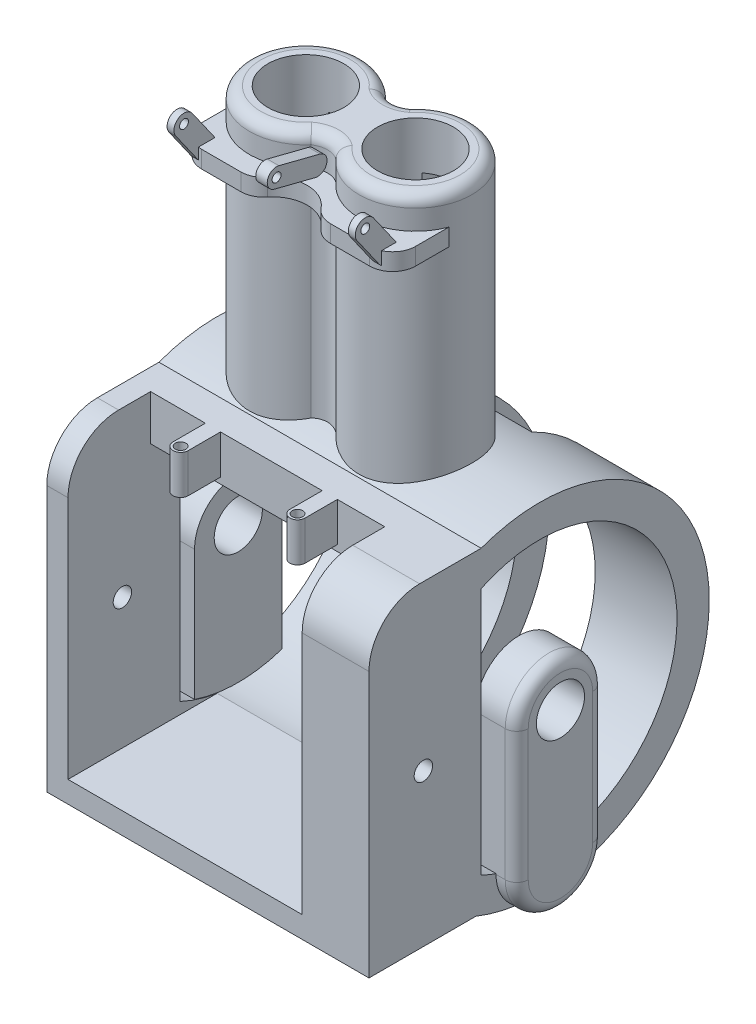
SolidWorks part; units mm, degrees
ref_plane "Ön Düzlem" through (0, 0, 0) normal (0, 0, 1) x (1, 0, 0)
ref_plane "Üst Düzlem" through (0, 0, 0) normal (0, 1, 0) x (1, 0, 0)
ref_plane "Sağ Düzlem" through (0, 0, 0) normal (1, 0, 0) x (0, 0, -1)
sketch "Çizim2" plane through (0, 0, 0) normal (0, 1, 0) x (1, 0, 0)
  line L0 (-55, 0) -> (55, 0) construction
  circle A0 centre (0, 0) radius 16.5
  circle A1 centre (-47.6265, 0) radius 16.5
  arc A2 (-29.2049, 16.1522) -> (-29.2049, -16.1522) centre (-47.6265, 0) ccw
  arc A3 (-18.4217, -16.1522) -> (-18.4217, 16.1522) centre (0, 0) ccw
  arc A4 (-29.2049, -16.1522) -> (-18.4217, -16.1522) centre (-23.8133, -23.9147) cw
  arc A5 (-29.2049, 16.1522) -> (-18.4217, 16.1522) centre (-23.8133, 23.9147) ccw
  circle A6 centre (-47.6265, 0) radius 24.5 construction
  circle A7 centre (0, 0) radius 24.5 construction
  point P5 (0, 0)
  point P10 (0, 0)
  point P19 (-29.2049, 16.1522)
  point P21 (0, 0)
  point P22 (-48.2806, 0)
  dimension "D1" = 33
  dimension "D2" = 8
  dimension "D3" = 8
extrude "Yükseklik-Ekstrüzyon1" add sketch "Çizim2" along normal blind 120 contours A5 A2 A4 A3 A1 A0 region at (-23.8133, 0, 0)
ref_plane "Düzlem1" through (0, 0, -32.0546) normal (0, 0, 1) x (1, 0, 0)
sketch "Çizim3" plane through (0, 0, -32.0546) normal (0, 0, 1) x (1, 0, 0)
  line L1 (10.3867, 99.4019) -> (-10.1113, 99.4019)
  line L2 (10.3867, 99.4019) -> (10.3867, 32.5179)
  line L3 (10.3867, 32.5179) -> (-10.1113, 32.5179)
  line L4 (-10.1113, 99.4019) -> (-10.1113, 32.5179)
  line L5 (-33.6449, 99.4019) -> (-53.2176, 99.4019)
  line L6 (-33.6449, 99.4019) -> (-33.6449, 32.5179)
  line L7 (-33.6449, 32.5179) -> (-53.2176, 32.5179)
  line L8 (-53.2176, 99.4019) -> (-53.2176, 32.5179)
extrude "Kes-Ekstrüzyon1" cut sketch "Çizim3" along normal blind 26
sketch "Çizim6" plane through (0, 0, 0) normal (1, 0, 0) x (0, 0, -1)
  circle A0 centre (0, -59.6459) radius 59.6459
  circle A1 centre (0, -59.6459) radius 73.6459
  point P5 (0, 0)
  point P6 (0, 0)
  dimension "D1" = 14
extrude "Yükseklik-Ekstrüzyon2" add sketch "Çizim6" along normal blind 54 and the other way blind 86
sketch "Çizim7" plane through (0, 120, 0) normal (0, 1, 0) x (1, 0, 0)
  circle A0 centre (-47.6265, 0) radius 16.5
  circle A1 centre (0, 0) radius 16.5
extrude "Kes-Ekstrüzyon3" cut sketch "Çizim7" against normal blind 228
sketch "Çizim8" plane through (0, 120, 0) normal (0, 1, 0) x (1, 0, 0)
  line L0 (-77, 32.0546) -> (77, 32.0546) construction
  line L1 (-66.2257, 93.0344) -> (-33.3817, 93.0344)
  line L2 (-66.2257, 93.0344) -> (-66.2257, 32.0546)
  line L3 (-66.2257, 32.0546) -> (-33.3817, 32.0546)
  line L4 (-33.3817, 93.0344) -> (-33.3817, 32.0546)
  line L5 (-15.5317, 93.2129) -> (18.4546, 93.2129)
  line L6 (-15.5317, 93.2129) -> (-15.5317, 32.0546)
  line L7 (-15.5317, 32.0546) -> (18.4546, 32.0546)
  line L8 (18.4546, 93.2129) -> (18.4546, 32.0546)
  line L10 (-54.9588, -91.8557) -> (17.8794, -91.8557)
  line L11 (-54.9588, -91.8557) -> (-54.9588, -45.5266)
  line L12 (-54.9588, -45.5266) -> (17.8794, -45.5266)
  line L13 (17.8794, -91.8557) -> (17.8794, -45.5266)
extrude "Kes-Ekstrüzyon4" cut sketch "Çizim8" against normal blind 290
sketch "Çizim9" plane through (0, 0, 0) normal (1, 0, 0) x (0, 0, -1)
  line L1 (-32.9089, 106.3109) -> (0.9157, 106.3109)
  line L2 (-32.9089, 106.3109) -> (-32.9089, 98.8674)
  line L3 (-32.9089, 98.8674) -> (0.9157, 98.8674)
  line L4 (0.9157, 106.3109) -> (0.9157, 98.8674)
extrude "Yükseklik-Ekstrüzyon3" add sketch "Çizim9" along normal blind 23 and the other way blind 70
fillet "Radyus1" radius 10 2 edges at (23, 102.5892, 32.9089) (-70, 102.5892, 32.9089)
sketch "Çizim10" plane through (0, 120, 0) normal (0, 1, 0) x (1, 0, 0)
  circle A0 centre (0, 0) radius 16.5 construction
  circle A1 centre (-47.6265, 0) radius 16.5 construction
  circle A2 centre (0, 0) radius 16.5
  circle A3 centre (-47.6265, 0) radius 16.5
extrude "Kes-Ekstrüzyon5" cut sketch "Çizim10" against normal blind 37
sketch "Çizim11" plane through (0, 106.3109, 0) normal (0, 1, 0) x (1, 0, 0)
  line L0 (-60, -32.9089) -> (13, -32.9089) construction
  line L1 (-37.3649, -32.9089) -> (-9.6617, -32.9089)
  arc A0 (-37.3649, -32.9089) -> (-9.6617, -32.9089) centre (-23.5133, -38.4571) cw
extrude "Kes-Ekstrüzyon6" cut sketch "Çizim11" against normal blind 37
fillet "Radyus2" radius 10 2 edges at (-9.6617, 102.5892, 32.9089) (-37.3649, 102.5892, 32.9089)
ref_plane "Düzlem2" through (17.2344, 0, 0) normal (1, 0, 0) x (0, 0, -1)
ref_plane "Düzlem3" through (-64.5268, 0, 0) normal (1, 0, 0) x (0, 0, -1)
sketch "Çizim14" plane through (-64.5268, 0, 0) normal (1, 0, 0) x (0, 0, -1)
  line L0 (-39.0408, 117.8786) -> (-29.5117, 104.3179) construction
  line L1 (-35.4786, 120.3818) -> (-25.9494, 106.8211)
  line L2 (-42.6031, 115.3754) -> (-33.0739, 101.8147)
  arc A0 (-35.4786, 120.3818) -> (-42.6031, 115.3754) centre (-39.0408, 117.8786) ccw
  arc A1 (-33.0739, 101.8147) -> (-25.9494, 106.8211) centre (-29.5117, 104.3179) ccw
  point P2 (-34.2762, 111.0983)
extrude "Yükseklik-Ekstrüzyon4" add sketch "Çizim14" along normal blind 3
sketch "Çizim15" plane through (17.2344, 0, 0) normal (1, 0, 0) x (0, 0, -1)
  line L0 (-42.6031, 115.3754) -> (-33.0739, 101.8147) construction
  line L1 (-25.9494, 106.8211) -> (-35.4786, 120.3818) construction
  line L2 (-42.6031, 115.3754) -> (-33.0739, 101.8147)
  line L3 (-25.9494, 106.8211) -> (-35.4786, 120.3818)
  line L6 (-25.9494, 106.8211) -> (-35.4786, 120.3818)
  line L7 (-42.6031, 115.3754) -> (-33.0739, 101.8147)
  line L8 (-25.9494, 106.8211) -> (-35.4786, 120.3818)
  line L9 (-42.6031, 115.3754) -> (-33.0739, 101.8147)
  arc A0 (-33.0739, 101.8147) -> (-31.8256, 100.6299) centre (-29.5117, 104.3179) ccw construction
  arc A1 (-35.4786, 120.3818) -> (-42.6031, 115.3754) centre (-39.0408, 117.8786) ccw construction
  arc A2 (-33.0739, 101.8147) -> (-31.8256, 100.6299) centre (-29.5117, 104.3179) ccw
  arc A3 (-35.4786, 120.3818) -> (-42.6031, 115.3754) centre (-39.0408, 117.8786) ccw
  arc A6 (-33.0739, 101.8147) -> (-25.9494, 106.8211) centre (-29.5117, 104.3179) ccw
  arc A7 (-35.4786, 120.3818) -> (-42.6031, 115.3754) centre (-39.0408, 117.8786) ccw
  arc A8 (-33.0739, 101.8147) -> (-25.9494, 106.8211) centre (-29.5117, 104.3179) ccw
  arc A9 (-35.4786, 120.3818) -> (-42.6031, 115.3754) centre (-39.0408, 117.8786) ccw
  dimension "D1" = 0
extrude "Yükseklik-Ekstrüzyon5" add sketch "Çizim15" against normal blind 3 contours A2 A8 L3 A3 L2 region at (17.2344, 111.0983, 34.2762)
sketch "Çizim16" plane through (17.2344, 0, 0) normal (1, 0, 0) x (0, 0, -1)
  circle A0 centre (-39.0492, 118.1335) radius 1.9404
extrude "Kes-Ekstrüzyon7" cut sketch "Çizim16" against normal blind 129
ref_plane "Düzlem4" through (-23.8, 0, 0) normal (1, 0, 0) x (0, 0, -1)
sketch "Çizim17" plane through (-23.8, 0, 0) normal (1, 0, 0) x (0, 0, -1)
  line L0 (-39.0492, 118.1335) -> (-21.1782, 113.5807) construction
  line L1 (-38.0478, 122.0642) -> (-20.1768, 117.5114)
  line L2 (-40.0506, 114.2028) -> (-22.1795, 109.65)
  arc A0 (-38.0478, 122.0642) -> (-40.0506, 114.2028) centre (-39.0492, 118.1335) ccw
  arc A1 (-22.1795, 109.65) -> (-20.1768, 117.5114) centre (-21.1782, 113.5807) ccw
  circle A2 centre (-39.0492, 118.1335) radius 1.9404 construction
  circle A3 centre (-39.0492, 118.1335) radius 1.9404
  point P3 (-30.1137, 115.8571)
extrude "Yükseklik-Ekstrüzyon6" add sketch "Çizim17" along normal mid plane 5 separate body
sketch "Çizim18" plane through (54, 0, 0) normal (1, 0, 0) x (0, 0, -1)
  line L0 (0, -116.5192) -> (0, -59.6459) construction
  line L1 (-18.9961, -116.5192) -> (-18.9961, -59.6459)
  line L2 (18.9961, -116.5192) -> (18.9961, -59.6459)
  arc A0 (-18.9961, -116.5192) -> (18.9961, -116.5192) centre (0, -116.5192) ccw
  arc A1 (18.9961, -59.6459) -> (-18.9961, -59.6459) centre (0, -59.6459) ccw
  circle A2 centre (0, -59.6459) radius 10.4598
  point P3 (0, -88.0825)
extrude "Yükseklik-Ekstrüzyon7" add sketch "Çizim18" along normal mid plane 18
sketch "Çizim19" plane through (-86, 0, 0) normal (-1, 0, 0) x (0, 0, 1)
  line L0 (-18.9961, -116.5192) -> (-18.9961, -59.6459) construction
  line L1 (-18.9961, -116.5192) -> (-18.9961, -59.6459)
  line L2 (18.9961, -116.5192) -> (18.9961, -59.6459) construction
  line L3 (18.9961, -116.5192) -> (18.9961, -59.6459)
  circle A0 centre (0, -59.6459) radius 10.4598 construction
  arc A1 (18.9961, -59.6459) -> (-18.9961, -59.6459) centre (0, -59.6459) ccw construction
  circle A2 centre (0, -59.6459) radius 10.4598
  arc A3 (18.9961, -59.6459) -> (-18.9961, -59.6459) centre (0, -59.6459) ccw
  arc A4 (-18.9961, -116.5192) -> (18.9961, -116.5192) centre (0, -116.5192) ccw construction
  circle A5 centre (0, -59.6459) radius 73.6459 construction
  arc A6 (-18.9961, -116.5192) -> (18.9961, -116.5192) centre (0, -116.5192) ccw
  circle A7 centre (0, -59.6459) radius 73.6459
  circle M1 centre (0, -59.6459) radius 59.6459
  circle M2 centre (0, -59.6459) radius 73.6459
extrude "Yükseklik-Ekstrüzyon8" add sketch "Çizim19" along normal mid plane 18 contours L3 A3 L1 A2 M1 | L1 A6 L3 M2 M1 region at (-86, -124.9458, 0) region at (-86, -84.4294, 0)
fillet "Radyus3" radius 5 4 edges at (-23.8133, 120, 14.4634) (-23.8133, 120, -14.4634) (24.5, 120, 0) (-72.1265, 120, 0)
fillet "Radyus5" radius 5 4 edges at (63, -135.5153, 0) (63, -88.0825, 18.9961) (63, -40.6498, 0) (63, -88.0825, -18.9961)
fillet "Radyus6" radius 2 5 edges at (-95, -125.6989, 16.6308) (-95, -88.0825, 18.9961) (-95, -125.6989, -16.6308) (-95, -88.0825, -18.9961) (-95, -40.6498, 0)
sketch "Çizim20" plane through (54, 0, 0) normal (1, 0, 0) x (0, 0, -1)
  line L0 (-25.464, 9.4577) -> (-74.2014, 9.4577)
  line L1 (-25.464, 9.4577) -> (-25.464, -127.8857)
  line L2 (-74.2014, 9.4577) -> (-74.2014, -127.8857)
  line L3 (-25.464, -127.8857) -> (-74.2014, -127.8857)
  circle A0 centre (0, -59.6459) radius 73.6459 construction
extrude "Yükseklik-Ekstrüzyon9" add sketch "Çizim20" against normal blind 140
sketch "Çizim21" plane through (0, 9.4577, 0) normal (0, 1, 0) x (1, 0, 0)
  line L0 (-76.7794, -74.2014) -> (24.9661, -74.2014)
  line L1 (-76.7794, -74.2014) -> (-76.7794, -38.3195)
  line L2 (24.9661, -74.2014) -> (24.9661, -38.3195)
  line L3 (-76.7794, -38.3195) -> (24.9661, -38.3195)
  line L4 (-86, -74.2014) -> (54, -74.2014) construction
extrude "Kes-Ekstrüzyon8" cut sketch "Çizim21" against normal blind 128
sketch "Çizim22" plane through (0, 0, 38.3195) normal (0, 0, 1) x (1, 0, 0)
  line L0 (-76.7794, -118.5423) -> (24.9661, -118.5423)
  line L1 (-76.7794, -118.5423) -> (-76.7794, -10.1855)
  line L2 (24.9661, -118.5423) -> (24.9661, -10.1855)
  line L3 (-76.7794, -10.1855) -> (24.9661, -10.1855)
extrude "Kes-Ekstrüzyon9" cut sketch "Çizim22" against normal blind 42
sketch "Çizim23" plane through (54, 0, 0) normal (1, 0, 0) x (0, 0, -1)
  line L0 (-39.0492, 118.1335) -> (-39.0492, 77.2105) construction
  circle A0 centre (-50.5644, -61.758) radius 4
  point P3 (-50.5644, -61.758)
extrude "Kes-Ekstrüzyon10" cut sketch "Çizim23" against normal blind 161
fillet "Radyus7" radius 22 2 edges at (39.483, 9.4577, 74.2014) (-81.3897, 9.4577, 74.2014)
sketch "Çizim24" plane through (0, 9.4577, 0) normal (0, 1, 0) x (1, 0, 0)
  line L0 (-49.6861, -32.9089) -> (-49.6861, -52.3418) construction
  line L1 (-60, -32.9089) -> (-42.9897, -32.9089) construction
  line L2 (-46.3925, -32.9089) -> (-46.3925, -52.3418)
  line L3 (-52.9797, -32.9089) -> (-52.9797, -52.3418)
  line L4 (1.0868, -32.9089) -> (1.0868, -52.3418) construction
  line L5 (4.3804, -32.9089) -> (4.3804, -52.3418)
  line L6 (-2.2068, -32.9089) -> (-2.2068, -52.3418)
  arc A0 (-46.3925, -32.9089) -> (-52.9797, -32.9089) centre (-49.6861, -32.9089) ccw
  arc A1 (-52.9797, -52.3418) -> (-46.3925, -52.3418) centre (-49.6861, -52.3418) ccw
  arc A2 (4.3804, -32.9089) -> (-2.2068, -32.9089) centre (1.0868, -32.9089) ccw
  arc A3 (-2.2068, -52.3418) -> (4.3804, -52.3418) centre (1.0868, -52.3418) ccw
  point P4 (-49.6861, -42.6253)
  point P11 (1.0868, -42.6253)
  point P16 (0, 0)
extrude "Yükseklik-Ekstrüzyon10" add sketch "Çizim24" against normal blind 17
sketch "Çizim25" plane through (0, 9.4577, 0) normal (0, 1, 0) x (1, 0, 0)
  circle A0 centre (-49.6834, -52.3418) radius 2.2968
  circle A1 centre (1.0868, -52.3418) radius 2.2968
  point P2 (-49.6834, -52.2792)
  point P5 (1.0868, -52.3418)
  point P7 (0, 0)
extrude "Kes-Ekstrüzyon11" cut sketch "Çizim25" against normal blind 28
